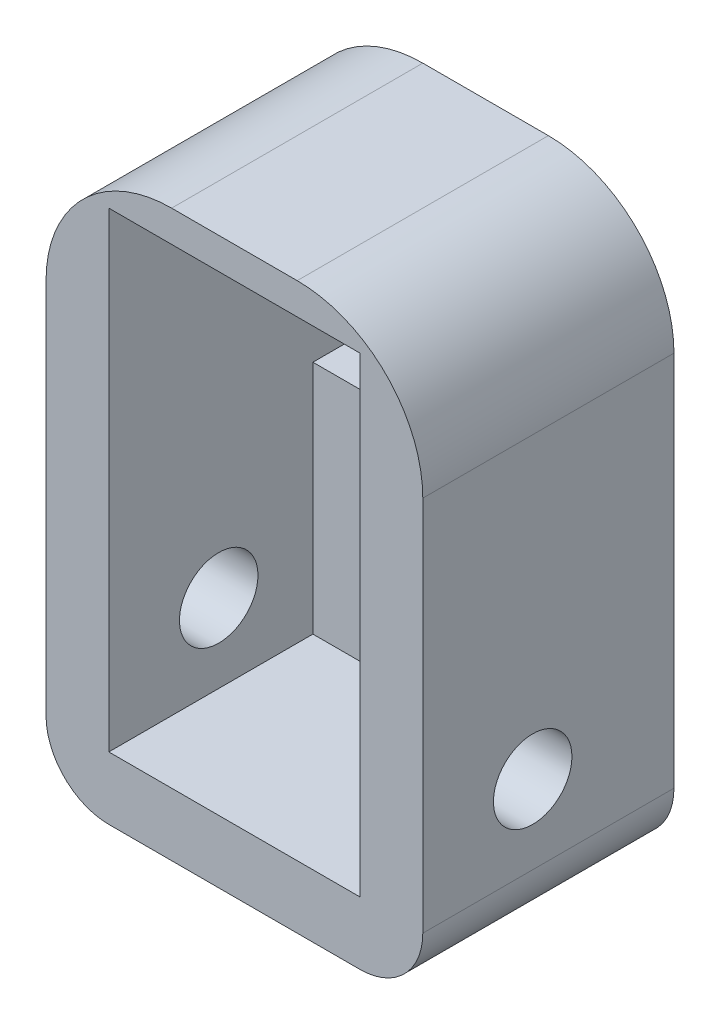
SolidWorks part; units mm, degrees
ref_plane "前视基准面" through (0, 0, 0) normal (0, 0, 1) x (1, 0, 0)
ref_plane "上视基准面" through (0, 0, 0) normal (0, 1, 0) x (1, 0, 0)
ref_plane "右视基准面" through (0, 0, 0) normal (1, 0, 0) x (0, 0, -1)
sketch "草图1" plane through (0, 0, 0) normal (0, 0, 1) x (1, 0, 0)
  line L0 (0, 0) -> (-2, 0)
  line L1 (-2, 0) -> (-2, -2)
  line L2 (8, 0) -> (10, 0)
  line L3 (10, 0) -> (10, -2)
  line L4 (10, -2) -> (-2, -2)
  line L5 (0, 15) -> (0, 16)
  line L6 (-2, 0) -> (-2, 16)
  line L7 (-2, 16) -> (0, 16)
  line L8 (0, 16) -> (10, 16)
  line L9 (10, 16) -> (10, 0)
  line L10 (0, 15) -> (8, 15)
  line L11 (8, 10) -> (8, 7.5)
  line L12 (8, 15) -> (8, 16)
  line L13 (8, 7.5) -> (0, 7.5)
  line L14 (8, 0) -> (8, 7.5)
  line L24 (0, 15) -> (0, 0)
  line L25 (0, 0) -> (8, 0)
  line L34 (8, 10) -> (8, 15)
extrude "凸台-拉伸1" add sketch "草图1" along normal blind 8 contours L24 L5 L7 L6 L0 | L10 L8 L5 | L34 L11 L14 L2 L9 L8 | L25 L0 L1 L4 L3 L2 region at (4, -1, 0) region at (-1, 8, 0) region at (9, 8, 0) region at (4, 15.5, 0)
extrude "凸台-拉伸2" add sketch "草图1<3>" along normal blind 1.5 contours L24 L25 L14 L13 region at (4, 3.75, 0)
sketch "草图1<3>" plane through (0, 0, 0) normal (0, 0, 1) x (1, 0, 0) same geometry as "草图1"
sketch "草图2" plane through (0, 0, 0) normal (1, 0, 0) x (0, 0, -1)
  line L0 (-2.5, 2.5) -> (-4.5, 2.5)
hole_wizard "M3 螺纹孔1" positions "草图3" profile "草图4" tap size "M3" standard "GB" end condition through all
sketch "草图3" plane through (10, 0, 0) normal (1, 0, 0) x (0, 0, -1)
  point P0 (-4.5, 2.5)
sketch "草图4" plane through (10, 2.5, 4.5) normal (0, 1, 0) x (0, 0, -1)
  line L0 (0, 0) -> (0, 12)
  line L1 (0, 12) -> (1.25, 12)
  line L2 (1.25, 12) -> (1.25, 0)
  line L5 (1.25, 0) -> (0, 0)
  line L11 (0, -6.35) -> (0, 107.95) construction
  dimension "通孔螺纹孔钻头直径" = 2.5
  dimension "通孔螺纹孔钻头深度" = 12
cosmetic thread "孔螺蚊线1" parameters "D2"=3
fillet "圆角2" radius 4 2 edges at (10, 16, 4) (-2, 16, 4)
fillet "圆角3" radius 2 2 edges at (10, -2, 4) (-2, -2, 4)
